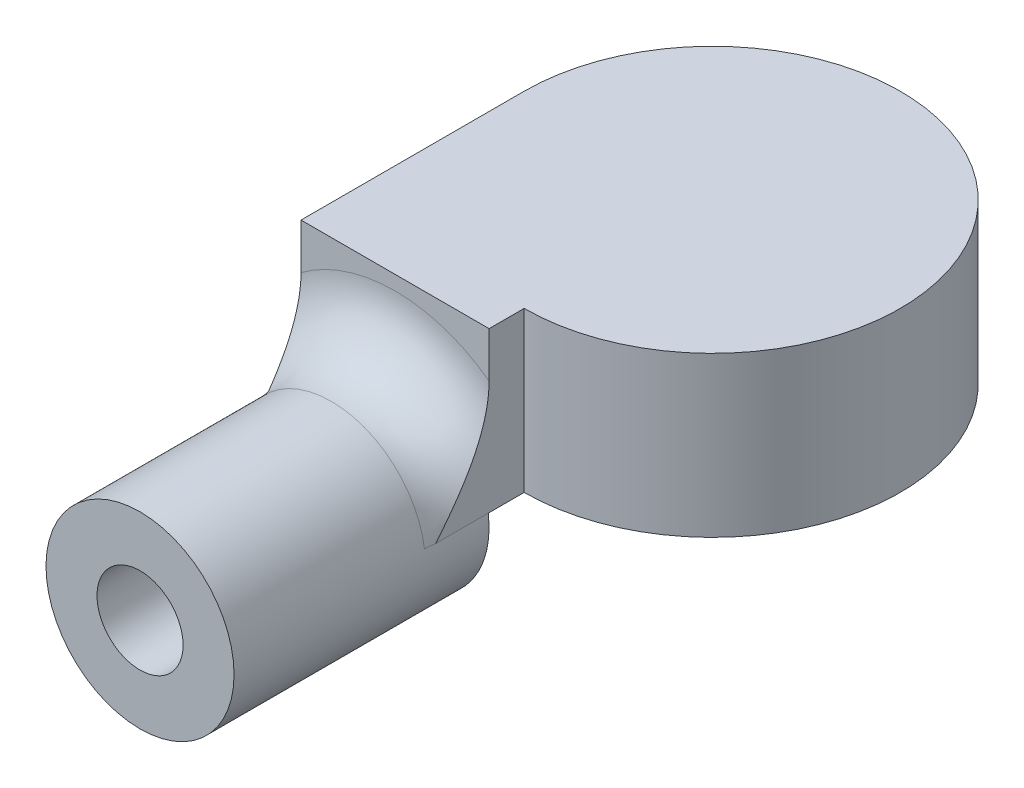
SolidWorks part; units mm, degrees
ref_plane "Front Plane" through (0, 0, 0) normal (0, 0, 1) x (1, 0, 0)
ref_plane "Top Plane" through (0, 0, 0) normal (0, 1, 0) x (1, 0, 0)
ref_plane "Right Plane" through (0, 0, 0) normal (1, 0, 0) x (0, 0, -1)
sketch "Sketch1" plane through (0, 0, 0) normal (0, 0, 1) x (1, 0, 0)
  circle A0 centre (0, 0) radius 1.7145
  circle A1 centre (0, 0) radius 3.7465
  dimension "D1" = 3.429
  dimension "D2" = 2.032
extrude "Boss-Extrude1" add sketch "Sketch1" along normal blind 10.16
sketch "Sketch2" plane through (0, 0, 0) normal (0, 1, 0) x (1, 0, 0)
  line L0 (3.7465, 0) -> (3.7465, 4.1752) construction
  line L1 (-3.7465, 0) -> (-3.7465, 8.89)
  line L2 (3.7465, 1.397) -> (3.7465, 0)
  line L3 (3.7465, 0) -> (-3.7465, 0)
  circle A0 centre (3.7465, 8.89) radius 4.7625
  circle A1 centre (3.7465, 8.89) radius 7.493
  dimension "D1" = 9.525
  dimension "D2" = 8.89
extrude "Boss-Extrude2" add sketch "Sketch2" along normal blind 6.35 from offset 0.508 contours A1 L1 L3 L2 | A1 A0 | A0 region at (-1.1092, 0, -1.9679) region at (3.7465, 0, -16.1711) region at (3.7465, 0, -8.89)
extrude "Cut-Extrude1" cut sketch "Sketch2<3>" along normal blind 4.4768 contours A0 region at (3.7465, 0, -8.89)
sketch "Sketch2<3>" plane through (0, 0, 0) normal (0, 1, 0) x (1, 0, 0) same geometry as "Sketch2"
fillet "Fillet1" radius 2.54 1 edges at (0, 3.7465, 0)
